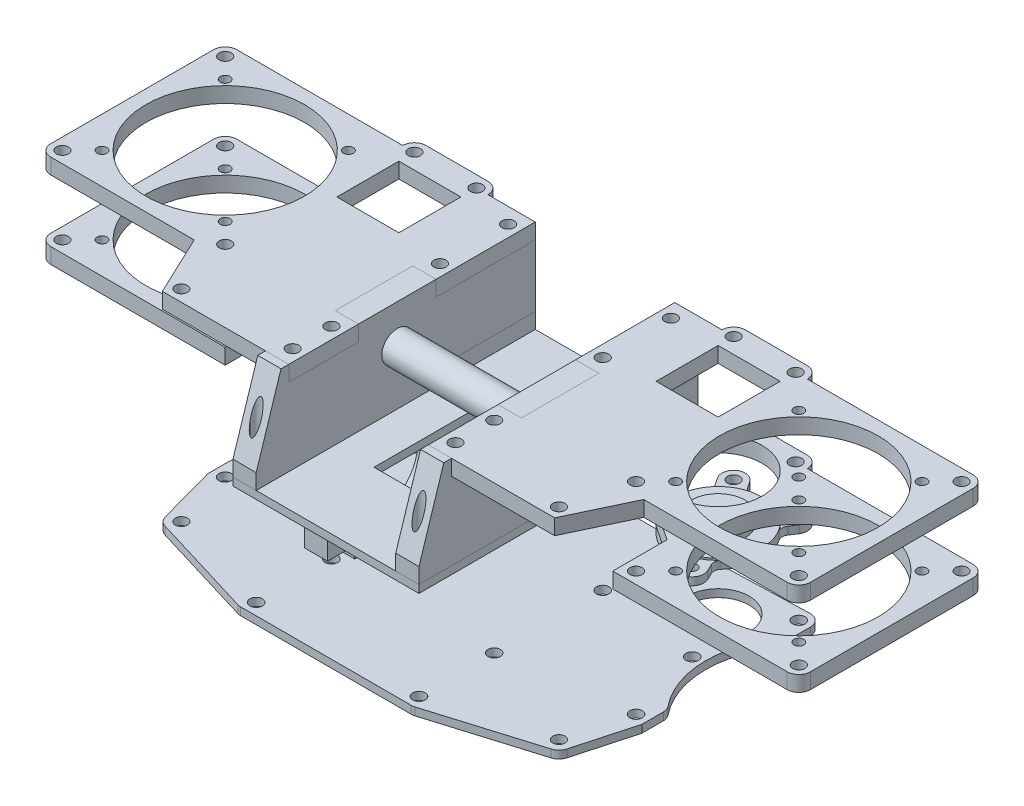
SolidWorks part; units mm, degrees
note: The reader was unsure of these and kept them because the rebuilt part matched: shared geometry of "Sketch14<2>".
material "Alum Plate"
ref_plane "Front Plane" through (0, 0, 0) normal (0, 0, 1) x (1, 0, 0)
ref_plane "Top Plane" through (0, 0, 0) normal (0, 1, 0) x (1, 0, 0)
ref_plane "Right Plane" through (0, 0, 0) normal (1, 0, 0) x (0, 0, -1)
sketch "Sketch1" plane through (0, 0, 0) normal (0, 1, 0) x (1, 0, 0)
  line L0 (0, 0) -> (117.475, 0) construction
  line L1 (-117.475, 0) -> (0, 0) construction
  line L3 (-9.525, 197.485) -> (-3.175, 197.485)
  line L4 (-9.525, 197.485) -> (-9.525, 70.485)
  line L5 (-9.525, 70.485) -> (-3.175, 70.485)
  line L6 (-3.175, 197.485) -> (-3.175, 70.485)
  line L7 (-9.525, 197.485) -> (-3.175, 70.485) construction
  line L8 (-9.525, 70.485) -> (-3.175, 197.485) construction
  line L14 (-155.575, -76.2) -> (155.575, -76.2)
  line L20 (-28.575, 38.1) -> (0, 38.1) construction
  line L21 (-6.35, 133.985) -> (0, 133.985)
  line L29 (0, 0) -> (0, -18.415) construction
  line L30 (-117.475, 0) -> (-65.3884, 19.05) construction
  line L43 (65.3884, 19.05) -> (117.475, 0) construction
  line L69 (-155.575, -76.2) -> (-155.575, 38.1)
  line L70 (-155.575, 38.1) -> (155.575, 38.1)
  line L71 (155.575, -76.2) -> (155.575, 38.1)
  line L78 (0, 133.985) -> (0, -18.415)
  line L79 (0, -18.415) -> (0, -170.815) construction
  line L80 (-9.525, -234.315) -> (-3.175, -234.315) construction
  line L81 (-9.525, -234.315) -> (-9.525, -107.315) construction
  line L82 (-9.525, -107.315) -> (-3.175, -107.315) construction
  line L83 (-3.175, -234.315) -> (-3.175, -107.315) construction
  line L84 (-9.525, -234.315) -> (-3.175, -107.315) construction
  line L85 (-9.525, -107.315) -> (-3.175, -234.315) construction
  line L86 (0, -170.815) -> (-6.35, -170.815) construction
  line L87 (-38.1, -76.2) -> (-28.575, -76.2)
  line L88 (-38.1, -76.2) -> (-38.1, 38.1)
  line L89 (-38.1, 38.1) -> (-28.575, 38.1)
  line L90 (-28.575, -76.2) -> (-28.575, 38.1)
  line L91 (38.1, -76.2) -> (28.575, -76.2)
  line L92 (38.1, -76.2) -> (38.1, 38.1)
  line L93 (38.1, 38.1) -> (28.575, 38.1)
  line L94 (28.575, -76.2) -> (28.575, 38.1)
  line L95 (0, 38.1) -> (28.575, 38.1) construction
  circle A0 centre (-117.475, 0) radius 32.5
  circle A1 centre (-117.475, 0) radius 25
  circle A2 centre (117.475, 0) radius 32.5
  circle A3 centre (117.475, 0) radius 25
  circle A4 centre (-65.3884, 19.05) radius 18
  circle A5 centre (65.3884, 19.05) radius 18
  point P8 (-6.35, 133.985)
  point P21 (117.475, 32.5)
  point P25 (65.3884, 37.05)
  point P29 (65.3884, 1.05)
  point P31 (0, -76.2)
  point P32 (-6.35, -170.815)
  point P62 (149.975, 0)
  dimension "D1" = 50
  dimension "D2" = 65
  dimension "D8" = 36
  dimension "D11" = 152.4
  dimension "D12" = 56.515
  dimension "D3" = 127
  dimension "D4" = 6.35
  dimension "D5" = 234.95
  dimension "D6" = 38.1
  dimension "D7" = 38.1
  dimension "D9" = 114.3
  dimension "D10" = 9.525
  dimension "D13" = 9.525
  dimension "D14" = 57.15
  dimension "D15" = 55.4609
  dimension "D18" = 19.05
sketch "Sketch2" plane through (0, 0, 0) normal (1, 0, 0) x (0, 0, -1)
  line L0 (0, 25.4) -> (0, 57.475) construction
  line L1 (-32.5, 60.975) -> (32.5, 60.975)
  line L2 (-32.5, 60.975) -> (-32.5, 53.975)
  line L3 (-32.5, 53.975) -> (32.5, 53.975)
  line L4 (32.5, 60.975) -> (32.5, 53.975)
  line L5 (-32.5, 60.975) -> (32.5, 53.975) construction
  line L6 (-32.5, 53.975) -> (32.5, 60.975) construction
  line L7 (-32.5, 92.075) -> (32.5, 92.075)
  line L8 (-32.5, 92.075) -> (-32.5, 85.075)
  line L9 (-32.5, 85.075) -> (32.5, 85.075)
  line L10 (32.5, 92.075) -> (32.5, 85.075)
  line L11 (-32.5, 92.075) -> (32.5, 85.075) construction
  line L12 (-32.5, 85.075) -> (32.5, 92.075) construction
  line L13 (-25.8191, 0) -> (33.9817, 0) construction
  line L14 (-18.415, 76.2) -> (-170.815, 76.2)
  line L15 (-76.2, 92.075) -> (38.1, 92.075)
  line L16 (-76.2, 92.075) -> (-76.2, 53.975)
  line L17 (-76.2, 53.975) -> (38.1, 53.975)
  line L18 (38.1, 92.075) -> (38.1, 53.975)
  line L19 (-5.8284, 26.8817) -> (0.4649, 73.66)
  line L20 (-18.415, 28.575) -> (-18.415, 76.2) construction
  line L21 (133.985, 0) -> (-18.415, 0) construction
  line L22 (-76.2, 85.725) -> (38.1, 85.725)
  line L23 (-76.2, 60.325) -> (38.1, 60.325)
  line L24 (-31.0016, 26.8817) -> (-37.2949, 73.66)
  line L25 (-18.415, 28.575) -> (-24.765, 64.8535) construction
  line L26 (-18.415, 76.2) -> (133.985, 76.2)
  line L32 (-76.2, 9.525) -> (38.1, 9.525)
  line L33 (-76.2, 9.525) -> (-76.2, 6.35)
  line L38 (-76.2, 6.35) -> (38.1, 6.35)
  line L39 (38.1, 9.525) -> (38.1, 6.35)
  line L40 (1.05, 41.2242) -> (37.05, 41.2242)
  line L41 (1.05, 41.2242) -> (1.05, 85.725)
  line L42 (1.05, 85.725) -> (37.05, 85.725)
  line L43 (37.05, 41.2242) -> (37.05, 85.725)
  line L44 (1.05, 41.2242) -> (37.05, 85.725) construction
  line L45 (1.05, 85.725) -> (37.05, 41.2242) construction
  line L46 (-38.1, 92.075) -> (-38.1, 53.975)
  line L47 (-38.1, 73.025) -> (0, 73.025) construction
  line L48 (0, 73.025) -> (38.1, 73.025) construction
  line L49 (-76.2, 9.525) -> (38.1, 6.35) construction
  line L50 (-76.2, 6.35) -> (38.1, 9.525) construction
  circle A0 centre (0, 25.4) radius 25.4
  circle A3 centre (-170.815, 76.2) radius 63.5
  circle A4 centre (-18.415, 76.2) radius 6.35
  circle A5 centre (-18.415, 28.575) radius 18
  circle A6 centre (133.985, 76.2) radius 63.5
  circle A7 centre (-18.415, 76.2) radius 19.05
  circle A8 centre (-18.415, 28.575) radius 12.7
  circle A9 centre (-24.765, 64.8535) radius 17.5006
  point P2 (0, 57.475)
  point P8 (0, 88.575)
  point P16 (-0.415, 28.575)
  point P28 (-36.415, 28.575)
  point P32 (19.05, 63.4746)
  point P34 (-234.315, 76.2)
  point P47 (0, 50.8)
  point P57 (-19.05, 7.9375)
  dimension "D1" = 50.8
  dimension "D8" = 38.1
  dimension "D2" = 25.4
  dimension "D11" = 12.7
  dimension "D12" = 36
  dimension "D14" = 35.0012
  dimension "D17" = 36.83
  dimension "D3" = 7
  dimension "D4" = 3.175
  dimension "D6" = 6.35
  dimension "D7" = 6.35
  dimension "D9" = 76.2
  dimension "D10" = 44.5008
  dimension "D13" = 47.625
  dimension "D15" = 3.175
  dimension "D16" = 25.4
  dimension "D18" = 44.45
  dimension "D19" = 6.35
sketch "Sketch5" plane through (0, 0, 0) normal (0, 1, 0) x (1, 0, 0)
  line L0 (-100.076, -18.415) -> (-28.575, -18.415) construction
  line L1 (-100.076, -4.415) -> (-68.58, -4.415)
  line L2 (-100.076, -4.415) -> (-100.076, -32.415)
  line L3 (-100.076, -32.415) -> (-68.58, -32.415)
  line L4 (-68.58, -4.415) -> (-68.58, -32.415)
  line L5 (-100.076, -4.415) -> (-68.58, -32.415) construction
  line L6 (-100.076, -32.415) -> (-68.58, -4.415) construction
  line L11 (-28.575, -76.2) -> (-28.575, 38.1) construction
  line L13 (-68.58, -0.415) -> (-28.575, -0.415)
  line L14 (-68.58, -0.415) -> (-68.58, -36.415)
  line L15 (-68.58, -36.415) -> (-28.575, -36.415)
  line L16 (-28.575, -0.415) -> (-28.575, -36.415)
  line L17 (-68.58, -0.415) -> (-28.575, -36.415) construction
  line L18 (-68.58, -36.415) -> (-28.575, -0.415) construction
  point P0 (-84.328, -18.415)
  point P10 (-48.5775, -18.415)
  dimension "D1" = 40.005
  dimension "D2" = 31.496
  dimension "D3" = 28
ref_plane "Plane1" through (0, 85.725, 0) normal (0, 1, 0) x (1, 0, 0)
ref_plane "Plane2" through (0, 60.325, 0) normal (0, -1, 0) x (-1, 0, 0)
ref_plane "Plane3" through (28.575, 0, 0) normal (1, 0, 0) x (0, 0, -1)
sketch "Sketch6" plane through (28.575, 0, 0) normal (1, 0, 0) x (0, 0, -1)
  line L0 (-18.415, 92.075) -> (-18.415, 76.2) construction
  line L2 (-76.2, 60.325) -> (-66.04, 92.075)
  line L3 (-76.2, 92.075) -> (38.1, 92.075) construction
  line L4 (-66.04, 92.075) -> (-62.865, 92.075)
  line L5 (-62.865, 92.075) -> (-62.865, 85.725)
  line L6 (-76.2, 85.725) -> (38.1, 85.725) construction
  line L7 (-62.865, 85.725) -> (-34.29, 85.725)
  line L8 (-2.54, 60.325) -> (-2.54, 53.975)
  line L10 (-32.5, 53.975) -> (32.5, 53.975) construction
  line L11 (-76.2, 53.975) -> (-76.2, 60.325)
  line L12 (-76.2, 53.975) -> (-2.54, 53.975)
  line L13 (-34.29, 85.725) -> (-34.29, 92.075)
  line L14 (-34.29, 92.075) -> (-2.54, 92.075)
  line L15 (-2.54, 85.725) -> (-2.54, 92.075)
  line L16 (-34.29, 85.725) -> (-2.54, 92.075) construction
  line L17 (-34.29, 92.075) -> (-2.54, 85.725) construction
  line L19 (-76.2, 60.325) -> (38.1, 60.325) construction
  line L20 (-2.54, 60.325) -> (38.1, 60.325)
  line L21 (-2.54, 60.325) -> (-2.54, 85.725) construction
  line L22 (-2.54, 85.725) -> (38.1, 85.725)
  line L23 (38.1, 60.325) -> (38.1, 85.725)
  line L24 (-2.54, 60.325) -> (38.1, 85.725) construction
  line L25 (-2.54, 85.725) -> (38.1, 60.325) construction
  line L26 (-2.54, 85.725) -> (-2.54, 60.325) construction
  point P10 (-18.415, 88.9)
  point P28 (17.78, 73.025)
  dimension "D2" = 44.45
  dimension "D3" = 3.175
  dimension "D4" = 31.75
extrude "Boss-Extrude1" add sketch "Sketch6" along normal up to vertex (9.525 mm away) up to point (38.1, 0, -38.1)
sketch "Sketch7" plane through (0, 85.725, 0) normal (0, 1, 0) x (1, 0, 0)
  line L0 (28.575, -62.865) -> (80.3409, -62.865)
  line L2 (155.575, -76.2) -> (155.575, 38.1) construction
  line L3 (155.575, -38.1) -> (155.575, 38.1)
  line L4 (155.575, 38.1) -> (28.575, 38.1)
  line L5 (28.575, 38.1) -> (28.575, -2.54)
  line L6 (155.575, -38.1) -> (117.475, -38.1)
  line L8 (117.475, 38.1) -> (117.475, 0) construction
  line L9 (117.475, 0) -> (117.475, -38.1) construction
  line L10 (28.575, -34.29) -> (38.1, -34.29)
  line L11 (38.1, -34.29) -> (38.1, -2.54)
  line L12 (38.1, -2.54) -> (28.575, -2.54)
  line L13 (28.575, -76.2) -> (28.575, 38.1) construction
  line L14 (28.575, -34.29) -> (28.575, -62.865)
  line L15 (117.475, -38.1) -> (92.075, -38.1)
  line L16 (92.075, -38.1) -> (80.3409, -62.865)
  circle A0 centre (117.475, 0) radius 32.5 construction
  circle A1 centre (117.475, 0) radius 32.5
  circle A3 centre (65.3884, 19.05) radius 3.175
  dimension "D1" = 51.7659
  dimension "D2" = 6.35
  dimension "D3" = 25.4
extrude "Boss-Extrude2" add sketch "Sketch7" along normal up to surface (6.35 mm away) separate body up to face at (33.3375, 92.075, 64.4525)
sketch "Sketch8" plane through (0, 60.325, 0) normal (0, -1, 0) x (-1, 0, 0)
  line L1 (-79.375, -38.1) -> (-155.575, -38.1)
  line L2 (-79.375, -38.1) -> (-79.375, 38.1) construction
  line L3 (-79.375, 38.1) -> (-155.575, 38.1)
  line L4 (-155.575, -38.1) -> (-155.575, 38.1)
  line L5 (-79.375, -38.1) -> (-155.575, 38.1) construction
  line L6 (-79.375, 38.1) -> (-155.575, -38.1) construction
  line L7 (155.575, 38.1) -> (-155.575, 38.1) construction
  line L8 (-28.575, 38.1) -> (-79.375, 38.1)
  line L12 (-79.375, -38.1) -> (-79.375, -3.175)
  line L13 (-79.375, -3.175) -> (-38.1, -3.175)
  line L14 (-38.1, -76.2) -> (-38.1, 38.1) construction
  line L15 (-38.1, -3.175) -> (-38.1, -2.54)
  line L16 (-38.1, -2.54) -> (-28.575, -2.54)
  line L17 (-28.575, -2.54) -> (-28.575, 38.1)
  circle A0 centre (-117.475, 0) radius 32.5 construction
  circle A1 centre (-117.475, 0) radius 32.5
  circle A3 centre (-65.3884, 19.05) radius 18
  circle A4 centre (-65.3884, 19.05) radius 18 construction
  dimension "D1" = 22.225
extrude "Boss-Extrude3" add sketch "Sketch8" along normal up to vertex (6.35 mm away) separate body up to point (0, 53.975, -38.1)
sketch "Sketch14" plane through (0, 60.325, 0) normal (0, 1, 0) x (1, 0, 0)
  line L0 (65.3884, 38.1) -> (65.3884, 19.05) construction
  line L1 (78.0884, 42.8625) -> (52.6884, 42.8625)
  line L2 (28.575, 38.1) -> (155.575, 38.1) construction
  line L3 (73.3259, 38.1) -> (57.4509, 38.1)
  arc A0 (73.3259, 38.1) -> (78.0884, 42.8625) centre (78.0884, 38.1) ccw
  arc A1 (52.6884, 42.8625) -> (57.4509, 38.1) centre (52.6884, 38.1) ccw
  dimension "D1" = 9.525
  dimension "D2" = 25.4
extrude "Boss-Extrude4" add sketch "Sketch14" against normal up to surface (6.35 mm away) up to face at (117.475, 53.975, -32.5)
extrude "Boss-Extrude5" add sketch "Sketch14<2>" against normal up to surface (6.35 mm away) from surface at 31.75 up to face at (67.4066, 85.725, 19.939) starting at face at (65.3884, 92.075, -22.225)
sketch "Sketch14<2>" plane through (0, 60.325, 0) normal (0, 1, 0) x (1, 0, 0) same geometry as "Sketch14"
sketch "Sketch15" plane through (0, 53.975, 0) normal (0, -1, 0) x (1, 0, 0)
  line L2 (79.375, 38.1) -> (79.375, 3.175) construction
  line L3 (155.575, 38.1) -> (79.375, 38.1) construction
  line L4 (155.575, 76.2) -> (155.575, -38.1) construction
  line L5 (-155.575, -38.1) -> (155.575, -38.1) construction
  line L6 (150.8125, 38.1) -> (155.575, 38.1)
  line L7 (155.575, 38.1) -> (155.575, 33.3375)
  line L8 (150.8125, -38.1) -> (155.575, -38.1)
  line L9 (155.575, -38.1) -> (155.575, -33.3375)
  line L10 (33.3375, -38.1) -> (33.3375, -31.75) construction
  line L11 (33.3375, -31.75) -> (33.3375, -3.81) construction
  line L12 (33.3375, -3.81) -> (33.3375, 2.54) construction
  line L13 (38.1, 2.54) -> (28.575, 2.54) construction
  line L14 (33.3375, 2.54) -> (33.3375, -3.81) construction
  line L15 (33.3375, 34.29) -> (33.3375, 40.64) construction
  line L16 (33.3375, 40.64) -> (33.3375, 56.515) construction
  line L18 (38.1, 34.29) -> (28.575, 34.29) construction
  line L19 (38.1, 2.54) -> (28.575, 2.54) construction
  line L20 (33.3375, 2.54) -> (33.3375, -3.81) construction
  line L21 (77.3274, 62.865) -> (77.3274, 58.1025) construction
  line L22 (28.575, 62.865) -> (80.3409, 62.865) construction
  line L23 (77.3274, 58.1025) -> (81.6312, 60.1417) construction
  line L24 (80.3409, 62.865) -> (92.075, 38.1) construction
  line L25 (33.3375, 56.515) -> (33.3375, 62.865) construction
  line L26 (80.3409, 62.865) -> (28.575, 62.865) construction
  circle A0 centre (52.6884, -38.1) radius 2.4892
  circle A1 centre (78.0884, -38.1) radius 2.4892
  circle A4 centre (150.8125, -33.3375) radius 2.4892
  circle A5 centre (150.8125, 33.3375) radius 2.4892
  circle A6 centre (84.1375, 33.3375) radius 2.4892
  circle A7 centre (84.1375, 33.3375) radius 4.7625 construction
  arc A8 (155.575, 33.3375) -> (150.8125, 38.1) centre (150.8125, 33.3375) ccw
  arc A9 (150.8125, -38.1) -> (155.575, -33.3375) centre (150.8125, -33.3375) ccw
  arc A10 (155.575, -33.3375) -> (150.8125, -38.1) centre (150.8125, -33.3375) ccw construction
  arc A11 (150.8125, 38.1) -> (155.575, 33.3375) centre (150.8125, 33.3375) ccw construction
  circle A12 centre (33.3375, -31.75) radius 2.4892
  circle A14 centre (33.3375, -3.81) radius 2.4892
  circle A15 centre (33.3375, 40.64) radius 2.4892
  circle A16 centre (77.3274, 58.1025) radius 2.4892
  circle A17 centre (33.3375, 56.515) radius 2.4892
  dimension "D1" = 4.9784
  dimension "D2" = 9.525
  dimension "D3" = 6.35
  dimension "D4" = 6.35
  dimension "D5" = 4.7625
extrude "Cut-Extrude9" cut sketch "Sketch15" against normal through all
sketch "Sketch16" plane through (28.575, 0, 0) normal (-1, 0, 0) x (0, 0, 1)
  circle A0 centre (18.415, 76.2) radius 6.35 construction
  circle A1 centre (18.415, 76.2) radius 6.35
extrude "Cut-Extrude10" cut sketch "Sketch16" against normal up to next (9.525 mm away)
sketch "Sketch19" plane through (0, 53.975, 0) normal (0, -1, 0) x (1, 0, 0)
  line L0 (33.3375, 76.2) -> (33.3375, 71.4375) construction
  line L1 (38.1, 76.2) -> (28.575, 76.2) construction
  line L2 (33.3375, 71.4375) -> (38.1, 71.4375) construction
  line L3 (38.1, 76.2) -> (38.1, 2.54) construction
  circle A0 centre (33.3375, -3.81) radius 2.0193
  circle A1 centre (33.3375, -31.75) radius 2.0193
  circle A2 centre (33.3375, 40.64) radius 2.0193
  circle A3 centre (33.3375, 71.4375) radius 2.0193
  circle A4 centre (33.3375, 40.64) radius 2.4892 construction
  circle A5 centre (33.3375, 56.515) radius 2.0193
  dimension "D1" = 4.0386
extrude "Cut-Extrude11" cut sketch "Sketch19" against normal through all
sketch "Sketch22" plane through (0, 53.975, 0) normal (0, -1, 0) x (1, 0, 0)
  line L0 (150.8125, -33.3375) -> (84.1375, -33.3375) construction
  line L1 (84.1375, -33.3375) -> (84.1375, 33.3375) construction
  circle A0 centre (84.1375, -33.3375) radius 2.0193
  circle A1 centre (33.3375, -31.75) radius 2.0193 construction
extrude "Cut-Extrude12" cut sketch "Sketch22" against normal up to next (6.35 mm away)
sketch "Sketch41" plane through (0, 92.075, 0) normal (0, 1, 0) x (1, 0, 0)
  line L1 (92.249, 25.226) -> (142.701, 25.226) construction
  line L2 (92.249, 25.226) -> (92.249, -25.226) construction
  line L3 (92.249, -25.226) -> (142.701, -25.226) construction
  line L4 (142.701, 25.226) -> (142.701, -25.226) construction
  line L5 (92.249, 25.226) -> (142.701, -25.226) construction
  line L6 (92.249, -25.226) -> (142.701, 25.226) construction
  circle A0 centre (92.249, 25.226) radius 2.0193
  circle A1 centre (142.701, 25.226) radius 2.0193
  circle A2 centre (142.701, -25.226) radius 2.0193
  circle A3 centre (92.249, -25.226) radius 2.0193
  circle A4 centre (92.249, 25.226) radius 4.445 construction
  circle A5 centre (117.475, 0) radius 32.5 construction
  point P0 (117.475, 0)
  point P11 (94.494, 22.981)
  dimension "D1" = 4.0386
  dimension "D2" = 8.89
  dimension "D3" = 3.175
extrude "Cut-Extrude23" cut sketch "Sketch41" against normal through all
chamfer "Chamfer1" distance 12.7 distance2 19.05 1 edges at (79.375, 57.15, 3.175)
sketch "Sketch42" plane through (0, 92.075, 0) normal (0, 1, 0) x (1, 0, 0)
  line L1 (52.6884, 31.75) -> (78.0884, 31.75)
  line L2 (52.6884, 31.75) -> (52.6884, 6.35)
  line L3 (52.6884, 6.35) -> (78.0884, 6.35)
  line L4 (78.0884, 31.75) -> (78.0884, 6.35)
  line L5 (52.6884, 31.75) -> (78.0884, 6.35) construction
  line L6 (52.6884, 6.35) -> (78.0884, 31.75) construction
  point P0 (65.3884, 19.05)
  dimension "D1" = 25.4
  dimension "D2" = 25.4
extrude "Cut-Extrude24" cut sketch "Sketch42" against normal up to surface (6.35 mm away) up to face at (92.249, 85.725, -23.2067)
mirror "Mirror2" about plane through (0, 0, 0) normal (1, 0, 0) of bodies 139 162 161 106 108 111
sketch "Sketch17" plane through (38.1, 0, 0) normal (1, 0, 0) x (0, 0, -1)
  circle A0 centre (-18.415, 76.2) radius 6.35 construction
  circle A1 centre (-18.415, 76.2) radius 6.35
extrude "Boss-Extrude6" add sketch "Sketch17" against normal up to surface (76.2 mm away) separate body up to face at (-38.1, 76.2, 24.765)
sketch "Sketch24" plane through (0, 53.975, 0) normal (0, -1, 0) x (1, 0, 0)
  line L1 (-38.1, 76.2) -> (38.1, 76.2)
  line L2 (-38.1, 76.2) -> (-38.1, -38.1)
  line L3 (-38.1, -38.1) -> (38.1, -38.1)
  line L4 (38.1, 76.2) -> (38.1, -38.1)
  line L5 (-38.1, 76.2) -> (38.1, -38.1) construction
  line L6 (-38.1, -38.1) -> (38.1, 76.2) construction
  circle A0 centre (-33.3375, 71.4375) radius 2.5527
  circle A1 centre (33.3375, 71.4375) radius 2.5527
  circle A2 centre (33.3375, 40.64) radius 2.5527
  circle A3 centre (-33.3375, 40.64) radius 2.5527
  circle A4 centre (-33.3375, -3.81) radius 2.5527
  circle A5 centre (33.3375, -3.81) radius 2.5527
  circle A6 centre (33.3375, -31.75) radius 2.5527
  circle A7 centre (-33.3375, -31.75) radius 2.5527
  circle A8 centre (33.3375, 56.515) radius 2.5527
  circle A9 centre (-33.3375, 56.515) radius 2.5527
  point P4 (0, 19.05)
  dimension "D1" = 5.1054
extrude "Boss-Extrude8" add sketch "Sketch24" along normal blind 3.175 separate body
sketch "Sketch25" plane through (0, 53.975, 0) normal (0, 1, 0) x (1, 0, 0)
  line L1 (-12.7, -43.815) -> (12.7, -43.815)
  line L2 (-12.7, -43.815) -> (-12.7, 6.985)
  line L3 (-12.7, 6.985) -> (12.7, 6.985)
  line L4 (12.7, -43.815) -> (12.7, 6.985)
  line L5 (-12.7, -43.815) -> (12.7, 6.985) construction
  line L6 (-12.7, 6.985) -> (12.7, -43.815) construction
  line L7 (-28.575, -76.2) -> (-28.575, -2.54) construction
  point P4 (0, -18.415)
  dimension "D1" = 25.4
  dimension "D2" = 50.8
  dimension "D3" = 15.875
extrude "Cut-Extrude13" cut sketch "Sketch25" against normal through all
sketch "Sketch34" plane through (0, 53.975, 0) normal (0, -1, 0) x (1, 0, 0)
  line L2 (-38.1, 76.2) -> (-38.1, -38.1) construction
  line L3 (38.1, -38.1) -> (38.1, 76.2) construction
  line L4 (-75.2766, 1.4526) -> (75.2766, 1.4526) construction
  circle A0 centre (75.2766, 1.4526) radius 2.0193
  circle A1 centre (75.2766, 1.4526) radius 4.7625 construction
  circle A2 centre (-117.475, 0) radius 37.4609 construction
  circle A3 centre (33.3375, -3.81) radius 2.0193 construction
  circle A4 centre (65.3884, -19.05) radius 18 construction
  circle A6 centre (-75.2766, 1.4526) radius 4.7625 construction
  circle A7 centre (-75.2766, 1.4526) radius 2.0193
  circle A8 centre (-65.3884, -19.05) radius 18 construction
  circle A9 centre (42.8625, -15.7769) radius 2.0193
  circle A10 centre (42.8625, -15.7769) radius 4.7625 construction
  circle A11 centre (-42.8625, -15.7769) radius 2.0193
  circle A12 centre (-42.8625, -15.7769) radius 4.7625 construction
  dimension "D1" = 9.525
extrude "Cut-Extrude20" cut sketch "Sketch34" against normal up to next (6.35 mm away)
ref_plane "Plane4" through (0, 9.525, 0) normal (0, -1, 0) x (-1, 0, 0)
sketch "Sketch21" plane through (0, 9.525, 0) normal (0, -1, 0) x (-1, 0, 0)
  line L0 (-84.1375, -33.3375) -> (-84.1375, 33.3375) construction
  line L1 (-84.1375, 33.3375) -> (-33.3375, 31.75) construction
  line L2 (-33.3375, 31.75) -> (33.3375, 31.75) construction
  line L3 (33.3375, 31.75) -> (84.1375, 33.3375) construction
  line L4 (84.1375, 33.3375) -> (84.1375, -33.3375) construction
  line L5 (84.1375, -33.3375) -> (33.3375, -71.4375) construction
  line L6 (33.3375, -71.4375) -> (-33.3375, -71.4375) construction
  line L7 (-33.3375, -71.4375) -> (-84.1375, -33.3375) construction
  line L8 (-88.9, -35.7188) -> (-88.9, 38.2512)
  line L9 (-88.9, 38.2512) -> (-33.2631, 36.5125)
  line L10 (-33.2631, 36.5125) -> (33.2631, 36.5125)
  line L11 (33.2631, 36.5125) -> (88.9, 38.2512)
  line L12 (88.9, 38.2512) -> (88.9, -35.7188)
  line L14 (34.925, -76.2) -> (-34.925, -76.2)
  line L16 (-84.1375, -33.3375) -> (-77.3274, -58.1025) construction
  line L17 (-77.3274, -58.1025) -> (-33.3375, -71.4375) construction
  line L18 (33.3375, -71.4375) -> (77.3274, -58.1025) construction
  line L19 (77.3274, -58.1025) -> (84.1375, -33.3375) construction
  line L20 (-88.9, -35.7188) -> (-81.6, -62.2655)
  line L21 (88.9, -35.7188) -> (34.925, -76.2) construction
  line L22 (-34.925, -76.2) -> (-88.9, -35.7188) construction
  line L23 (-81.6, -62.2655) -> (-35.6323, -76.2)
  line L24 (35.6323, -76.2) -> (81.6, -62.2655)
  line L25 (81.6, -62.2655) -> (88.9, -35.7188)
  line L26 (-89.174, -34.7225) -> (-81.6, -62.2655) construction
  line L27 (81.6, -62.2655) -> (89.174, -34.7225) construction
  line L28 (-34.925, -76.2) -> (-35.6323, -76.2)
  line L31 (-38.1, -76.2) -> (38.1, -76.2) construction
  line L32 (-81.6, -62.2655) -> (-34.8528, -76.4363) construction
  line L33 (34.925, -76.2) -> (35.6323, -76.2)
  line L34 (34.8528, -76.4363) -> (81.6, -62.2655) construction
  circle A0 centre (-84.1375, 33.3375) radius 2.5527
  circle A1 centre (-84.1375, -33.3375) radius 2.5527
  circle A2 centre (-33.3375, 31.75) radius 2.5527
  circle A3 centre (-33.3375, 3.81) radius 2.5527
  circle A4 centre (-33.3375, -40.64) radius 2.5527
  circle A5 centre (-33.3375, -71.4375) radius 2.5527
  circle A6 centre (33.3375, -71.4375) radius 2.5527
  circle A7 centre (33.3375, -40.64) radius 2.5527
  circle A8 centre (33.3375, 3.81) radius 2.5527
  circle A9 centre (33.3375, 31.75) radius 2.5527
  circle A10 centre (84.1375, 33.3375) radius 2.5527
  circle A11 centre (84.1375, -33.3375) radius 2.5527
  circle A12 centre (-77.3274, -58.1025) radius 2.4892 construction
  circle A13 centre (77.3274, -58.1025) radius 2.4892 construction
  circle A15 centre (-77.3274, -58.1025) radius 2.4892
  circle A17 centre (-75.2766, -1.4526) radius 2.5527
  circle A18 centre (75.2766, -1.4526) radius 2.5527
  circle A19 centre (-42.8625, 15.7769) radius 2.5527
  circle A20 centre (42.8625, 15.7769) radius 2.5527
  circle A21 centre (77.3274, -58.1025) radius 2.4892
  dimension "D1" = 5.1054
  dimension "D2" = 4.7625
extrude "Boss-Extrude7" add sketch "Sketch21" along normal up to vertex (3.175 mm away) separate body up to point (0, 6.35, -38.1)
sketch "Sketch26" plane through (-38.1, 0, 0) normal (-1, 0, 0) x (0, 0, 1)
  line L0 (76.2, 9.525) -> (-38.1, 9.525) construction
  line L1 (-10.16, 9.525) -> (46.99, 9.525)
  line L2 (-10.16, 9.525) -> (-10.16, 50.8)
  line L3 (-10.16, 50.8) -> (46.99, 50.8)
  line L4 (46.99, 9.525) -> (46.99, 50.8)
  line L5 (-10.16, 9.525) -> (46.99, 50.8) construction
  line L6 (-10.16, 50.8) -> (46.99, 9.525) construction
  line L7 (76.2, 50.8) -> (-38.1, 50.8) construction
  line L8 (18.415, 28.575) -> (18.415, 30.1625) construction
  circle A0 centre (18.415, 28.575) radius 18 construction
  circle A1 centre (18.415, 28.575) radius 18
  point P7 (18.415, 30.1625)
  dimension "D1" = 57.15
extrude "Boss-Extrude9" add sketch "Sketch26" against normal up to surface (9.525 mm away) separate body up to face at (-28.575, 76.2, 24.765)
sketch "Sketch27" plane through (0, 9.525, 0) normal (0, -1, 0) x (1, 0, 0)
  circle A0 centre (-33.3375, -3.81) radius 2.5527 construction
  circle A1 centre (-33.3375, 40.64) radius 2.5527 construction
  circle A2 centre (-33.3375, -3.81) radius 2.5527
  circle A3 centre (-33.3375, 40.64) radius 2.5527
extrude "Cut-Extrude14" cut sketch "Sketch27" against normal through all
sketch "Sketch28" plane through (-38.1, 0, 0) normal (-1, 0, 0) x (0, 0, 1)
  line L0 (-6.3627, 6.35) -> (-1.2573, 6.35) construction
  line L1 (-10.16, 9.525) -> (0.9525, 9.525)
  line L2 (-10.16, 9.525) -> (-10.16, 14.2875)
  line L3 (-10.16, 14.2875) -> (0.9525, 14.2875)
  line L4 (0.9525, 9.525) -> (0.9525, 14.2875)
  line L5 (-10.16, 9.525) -> (0.9525, 14.2875) construction
  line L6 (-10.16, 14.2875) -> (0.9525, 9.525) construction
  line L7 (46.99, 9.525) -> (35.8775, 9.525)
  line L8 (46.99, 9.525) -> (46.99, 14.2875)
  line L9 (46.99, 14.2875) -> (35.8775, 14.2875)
  line L10 (35.8775, 9.525) -> (35.8775, 14.2875)
  line L11 (46.99, 9.525) -> (35.8775, 14.2875) construction
  line L12 (46.99, 14.2875) -> (35.8775, 9.525) construction
  line L13 (-6.3627, 6.35) -> (-1.2573, 6.35) construction
  point P4 (-4.6038, 11.9062)
  point P10 (41.4337, 11.9062)
  point P14 (-3.81, 6.35)
  dimension "D1" = 4.7625
  dimension "D2" = 4.7625
extrude "Cut-Extrude15" cut sketch "Sketch28" against normal through all
sketch "Sketch30" plane through (0, 6.35, 0) normal (0, -1, 0) x (1, 0, 0)
  line L0 (-33.3375, -3.81) -> (-33.3375, 5.715) construction
  line L1 (-33.3375, 5.715) -> (-33.3375, 31.115) construction
  line L2 (-33.3375, 31.115) -> (-33.3375, 40.64) construction
  circle A0 centre (-33.3375, 31.115) radius 2.5527
  circle A1 centre (-33.3375, 5.715) radius 2.5527
  circle A2 centre (-33.3375, -3.81) radius 2.5527 construction
  dimension "D1" = 9.525
extrude "Cut-Extrude16" cut sketch "Sketch30" against normal through all
sketch "Sketch31" plane through (0, 9.525, 0) normal (0, -1, 0) x (1, 0, 0)
  circle A0 centre (-33.3375, 5.715) radius 2.0193
  circle A1 centre (-33.3375, 31.115) radius 2.0193
  circle A2 centre (-33.3375, -3.81) radius 2.0193 construction
extrude "Cut-Extrude17" cut sketch "Sketch31" against normal up to next
sketch "Sketch32" plane through (-38.1, 0, 0) normal (-1, 0, 0) x (0, 0, 1)
  line L0 (46.99, 14.2875) -> (46.99, 50.8) construction
  line L1 (-10.16, 28.702) -> (46.99, 28.702)
  line L2 (-10.16, 28.702) -> (-10.16, 28.448)
  line L3 (-10.16, 28.448) -> (46.99, 28.448)
  line L4 (46.99, 28.702) -> (46.99, 28.448)
  line L5 (-10.16, 28.702) -> (46.99, 28.448) construction
  line L6 (-10.16, 28.448) -> (46.99, 28.702) construction
  point P0 (18.415, 28.575)
  dimension "D1" = 0.254
extrude "Cut-Extrude18" cut sketch "Sketch32" against normal through all
sketch "Sketch33" plane through (0, 6.35, 0) normal (0, -1, 0) x (1, 0, 0)
  line L0 (88.9, -38.2512) -> (88.9, 35.7188) construction
  line L1 (88.9, -25.2008) -> (88.9, 25.2008)
  line L2 (-88.9, 35.7188) -> (-88.9, -38.2512) construction
  line L3 (-88.9, -25.2008) -> (-88.9, 25.2008)
  arc A0 (88.9, -25.2008) -> (88.9, 25.2008) centre (117.475, 0) cw
  arc A1 (-88.9, 25.2008) -> (-88.9, -25.2008) centre (-117.475, 0) cw
  dimension "D1" = 38.1
extrude "Cut-Extrude19" cut sketch "Sketch33" against normal up to surface (3.175 mm away) up to face at (-33.3375, 9.525, 28.5623)
fillet "Fillet1" radius 4.7625 10 edges at (88.9, 7.9375, -38.2512) (88.9, 7.9375, 25.2008) (88.9, 7.9375, -25.2008) (-88.9, 7.9375, -25.2008) (-88.9, 7.9375, 25.2008) (-88.9, 7.9375, -38.2512) (-81.6, 7.9375, 62.2655) (-35.6323, 7.9375, 76.2) (35.6323, 7.9375, 76.2) (81.6, 7.9375, 62.2655)
ref_plane "Plane5" through (0, 41.275, 0) normal (0, -1, 0) x (-1, 0, 0)
sketch "Sketch35" plane through (0, 41.275, 0) normal (0, -1, 0) x (-1, 0, 0)
  line L0 (-65.3884, 19.05) -> (-78.0884, 38.1) construction
  line L1 (-52.6884, 38.1) -> (-65.3884, 19.05) construction
  line L2 (-65.3884, 19.05) -> (-42.8625, 15.7769) construction
  line L3 (-75.2766, -1.4526) -> (-65.3884, 19.05) construction
  line L4 (-79.5663, 0.6163) -> (-77.2187, 5.4837)
  line L5 (-78.9799, 30.8514) -> (-82.0511, 35.4582)
  line L6 (-48.7258, 35.4582) -> (-51.797, 30.8514)
  line L7 (-48.8951, 11.841) -> (-43.5473, 11.0639)
  line L8 (-70.9869, -3.5214) -> (-68.6394, 1.346)
  line L9 (-66.0733, 14.337) -> (-43.5473, 11.0639) construction
  line L10 (-56.6511, 40.7418) -> (-59.7223, 36.1349)
  line L11 (-66.0733, 14.337) -> (-67.5575, 14.5527)
  line L12 (-70.9869, -3.5214) -> (-61.0988, 16.9811) construction
  line L13 (-79.5663, 0.6163) -> (-69.6781, 21.1189) construction
  line L14 (-69.3511, 16.4082) -> (-82.0511, 35.4582) construction
  line L15 (-71.0546, 36.1349) -> (-74.1258, 40.7418)
  line L16 (-56.6511, 40.7418) -> (-69.3511, 21.6918) construction
  line L18 (-47.5255, 21.267) -> (-42.1777, 20.4899)
  line L19 (-48.7258, 35.4582) -> (-61.4258, 16.4082) construction
  circle A0 centre (-65.3884, 19.05) radius 18 construction
  arc A1 (-78.9799, 30.8514) -> (-77.2187, 5.4837) centre (-65.3884, 19.05) ccw
  arc A2 (-74.1258, 40.7418) -> (-82.0511, 35.4582) centre (-78.0884, 38.1) ccw
  arc A3 (-48.7258, 35.4582) -> (-56.6511, 40.7418) centre (-52.6884, 38.1) ccw
  arc A4 (-43.5473, 11.0639) -> (-42.1777, 20.4899) centre (-42.8625, 15.7769) ccw
  arc A5 (-79.5663, 0.6163) -> (-70.9869, -3.5214) centre (-75.2766, -1.4526) ccw
  arc A6 (-59.7223, 36.1349) -> (-71.0546, 36.1349) centre (-65.3884, 19.05) ccw
  arc A7 (-47.5255, 21.267) -> (-51.797, 30.8514) centre (-65.3884, 19.05) ccw
  arc A8 (-68.6394, 1.346) -> (-48.8951, 11.841) centre (-65.3884, 19.05) ccw
  circle A9 centre (-75.2766, -1.4526) radius 2.0193 construction
  circle A10 centre (-42.8625, 15.7769) radius 2.0193 construction
  circle A11 centre (-52.6884, 38.1) radius 2.4892 construction
  circle A12 centre (-78.0884, 38.1) radius 2.4892 construction
  circle A13 centre (-75.2766, -1.4526) radius 2.0193
  circle A14 centre (-42.8625, 15.7769) radius 2.0193
  circle A15 centre (-52.6884, 38.1) radius 2.4892
  circle A16 centre (-78.0884, 38.1) radius 2.4892
extrude "Boss-Extrude10" add sketch "Sketch35" along normal blind 3.175 separate body
sketch "Sketch36" plane through (0, 41.275, 0) normal (0, 1, 0) x (1, 0, 0)
  circle A0 centre (65.3884, 19.05) radius 18
  arc A1 (48.8951, 11.841) -> (68.6394, 1.346) centre (65.3884, 19.05) ccw construction
extrude "Boss-Extrude11" add sketch "Sketch36" along normal offset from surface (0.762 mm away) 3.937 up to face at (78.0884, 38.1, -40.5892)
sketch "Sketch37" plane through (0, 42.037, 0) normal (0, 1, 0) x (1, 0, 0)
  circle A0 centre (65.3884, 19.05) radius 10.9982
  circle A1 centre (65.3884, 19.05) radius 18 construction
  dimension "D1" = 21.9964
extrude "Boss-Extrude12" add sketch "Sketch37" along normal offset from surface (2.413 mm away) 6.35 up to face at (78.0884, 38.1, -40.5892)
sketch "Sketch38" plane through (0, 38.1, 0) normal (0, -1, 0) x (1, 0, 0)
  circle A0 centre (65.3884, -19.05) radius 3.9878
  dimension "D1" = 7.9756
extrude "Cut-Extrude21" cut sketch "Sketch38" against normal through all
fillet "Fillet2" radius 3.175 8 edges at (47.5255, 39.6875, -21.267) (51.797, 39.6875, -30.8514) (59.7223, 39.6875, -36.1349) (71.0546, 39.6875, -36.1349) (78.9799, 39.6875, -30.8514) (77.2187, 39.6875, -5.4837) (68.6394, 39.6875, -1.346) (48.8951, 39.6875, -11.841)
mirror "Mirror3" about plane through (0, 0, 0) normal (1, 0, 0) of bodies 157
sketch "Sketch39" plane through (0, 6.35, 0) normal (0, -1, 0) x (1, 0, 0)
  circle A0 centre (-65.3884, -19.05) radius 12.7
  circle A1 centre (65.3884, -19.05) radius 12.7
  circle A4 centre (65.3884, -19.05) radius 3.9878 construction
  circle A5 centre (-65.3884, -19.05) radius 3.9878 construction
  dimension "D1" = 25.4
extrude "Cut-Extrude22" cut sketch "Sketch39" against normal up to next (3.175 mm away)
